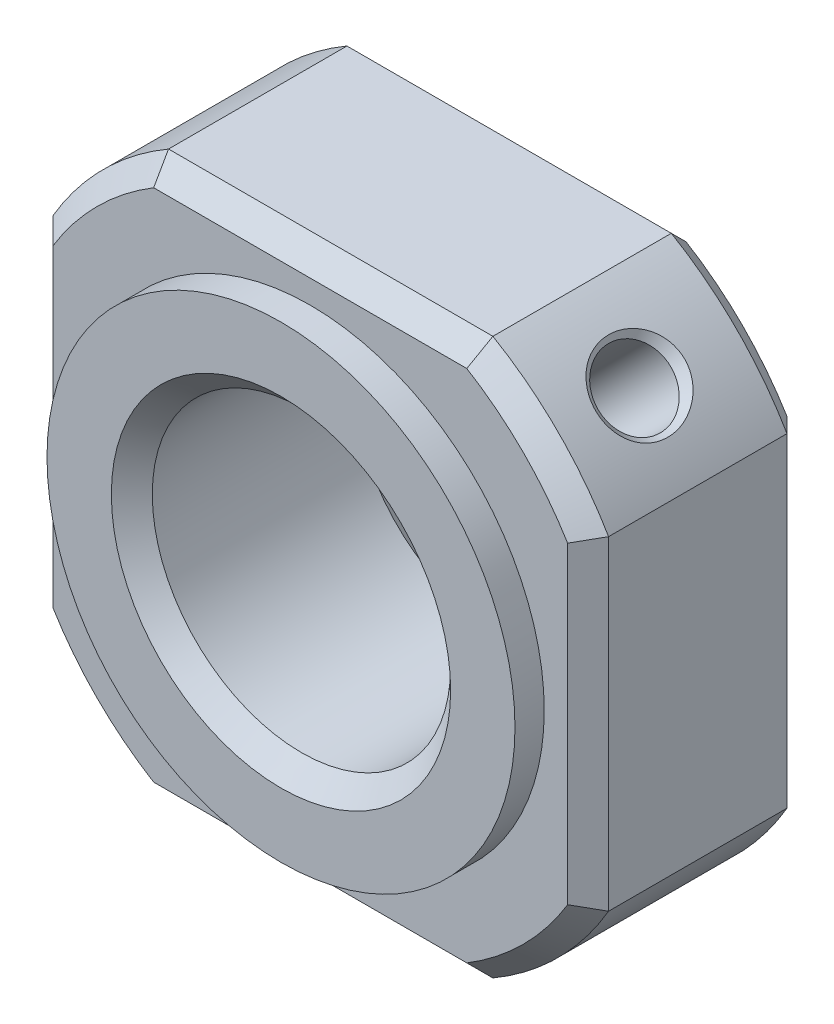
SolidWorks part; units mm, degrees
material "1060 Alloy"
ref_plane "Front" through (0, 0, 0) normal (0, 0, 1) x (1, 0, 0)
ref_plane "Top" through (0, 0, 0) normal (0, 1, 0) x (1, 0, 0)
ref_plane "Right" through (0, 0, 0) normal (1, 0, 0) x (0, 0, -1)
sketch "Sketch1" plane through (0, 0, 0) normal (0, 0, 1) x (1, 0, 0)
  line L1 (-9.5, 5.5453) -> (-9.5, -5.5453)
  line L2 (-5.5453, -9.5) -> (5.5453, -9.5)
  line L3 (9.5, -5.5453) -> (9.5, 5.5453)
  line L4 (5.5453, 9.5) -> (-5.5453, 9.5)
  arc A1 (-9.5, -5.5453) -> (-5.5453, -9.5) centre (0, 0) ccw
  arc A2 (5.5453, -9.5) -> (9.5, -5.5453) centre (0, 0) ccw
  arc A3 (9.5, 5.5453) -> (5.5453, 9.5) centre (0, 0) ccw
  arc A4 (-5.5453, 9.5) -> (-9.5, 5.5453) centre (0, 0) ccw
  dimension "D2" = 22
  dimension "D1" = 19
extrude "Boss-Extrude1" add sketch "Sketch1" against normal blind 8.5 contours L4 A4 L1 A1 L2 A2 L3 A3
sketch "Sketch2" plane through (0, 0, 0) normal (0, 0, 1) x (1, 0, 0)
  circle A0 centre (0, 0) radius 8
  dimension "D1" = 16
extrude "Cut-Extrude1" cut sketch "Sketch2" against normal blind 1 flip side to cut contours A0
chamfer "Chamfer2" distance 0.7 angle 45 16 edges at (0, 9.5, -8.5) (-7.7782, 7.7782, -8.5) (-9.5, 0, -8.5) (-7.7782, -7.7782, -8.5) (0, -9.5, -8.5) (7.7782, -7.7782, -8.5) (9.5, 0, -8.5) (7.7782, 7.7782, -8.5) (0, -9.5, -1) (-7.7782, -7.7782, -1) (-9.5, 0, -1) (7.7782, -7.7782, -1) (9.5, 0, -1) (7.7782, 7.7782, -1) (0, 9.5, -1) (-7.7782, 7.7782, -1)
hole_wizard "M12 Tapped Hole1" positions "Sketch8" profile "Sketch7" tap size "M12" standard "ISO"
sketch "Sketch8" plane through (0, 0, -8.5) normal (0, 0, -1) x (-1, 0, 0)
  point P0 (0, 0)
sketch "Sketch7" plane through (0, 0, -8.5) normal (1, 0, 0) x (0, 1, 0)
  line L0 (0, 0) -> (0, 13.0644)
  line L1 (0, 13.0644) -> (5.1, 10)
  line L2 (5.1, 10) -> (5.1, 0.925)
  line L3 (5.1, 0.925) -> (6.025, 0)
  line L5 (6.025, 0) -> (0, 0)
  line L6 (-5.1, 0.925) -> (-6.025, 0) construction
  line L10 (0, 13.0644) -> (-5.1, 10) construction
  line L11 (0, -6.35) -> (0, 107.95) construction
  dimension "Tap Drill Dia." = 10.2
  dimension "Tap Drill Depth" = 10
  dimension "Near C'Sink Dia." = 12.05
  dimension "Near C'Sink Angle" = 90
  dimension "Drill Angle" = 118
cosmetic thread "Hole Thread1" parameters "D1"=8.5, "D2"=12
chamfer "Chamfer3" distance 0.7 angle 45 1 edges at (5.1, 0, 0)
ref_axis "Axis1" through (0, 0, -0.7) along (0, 0, -1)
hole_wizard "M3 Tapped Hole5" positions "3DSketch26" profile "Sketch48" tap size "M3" standard "ISO"
sketch3d "3DSketch26"
  line L0 (0, 0, 0) -> (0, 0, -4.5) construction
  line L1 (0, 0, -4.5) -> (9.4419, 9.4419, -4.5) construction
  line L3 (0, 0, -4.5) -> (0, 13.6092, -4.5) construction
  point P0 (7.7782, 7.7782, -4.5)
  dimension "D1" = 4.5
  dimension "D2" = 45
sketch "Sketch48" plane through (7.7782, 7.7782, -4.5) normal (0, 0, 1) x (-0.7071, 0.7071, 0)
  line L0 (0, 0) -> (0, 8.2511)
  line L1 (0, 8.2511) -> (1.25, 7.5)
  line L2 (1.25, 7.5) -> (1.25, 0.275)
  line L3 (1.25, 0.275) -> (1.525, 0)
  line L5 (1.525, 0) -> (0, 0)
  line L6 (-1.25, 0.275) -> (-1.525, 0) construction
  line L10 (0, 8.2511) -> (-1.25, 7.5) construction
  line L11 (0, -6.35) -> (0, 107.95) construction
  dimension "Tap Drill Dia." = 2.5
  dimension "Tap Drill Depth" = 7.5
  dimension "Near C'Sink Dia." = 3.05
  dimension "Near C'Sink Angle" = 90
  dimension "Drill Angle" = 118
cosmetic thread "Hole Thread4" parameters "D1"=6.0556, "D2"=3
